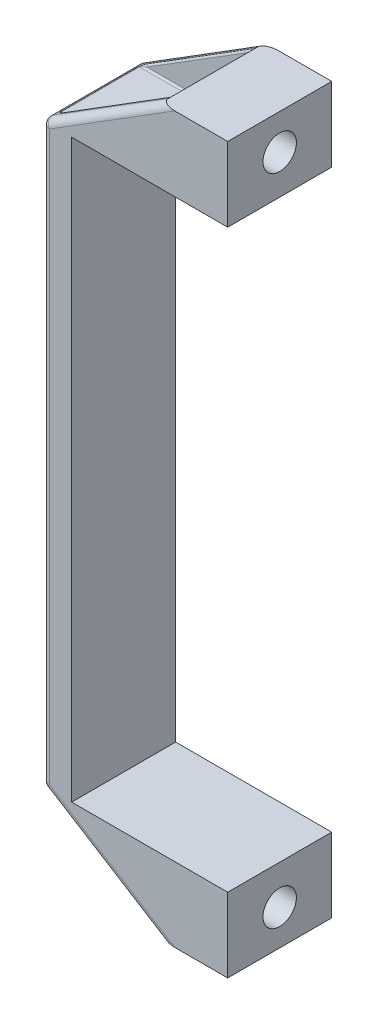
SolidWorks part; units mm, degrees
ref_plane "前视基准面" through (0, 0, 0) normal (0, 0, 1) x (1, 0, 0)
ref_plane "上视基准面" through (0, 0, 0) normal (0, 1, 0) x (1, 0, 0)
ref_plane "右视基准面" through (0, 0, 0) normal (1, 0, 0) x (0, 0, -1)
sketch "草图1" plane through (0, 0, 0) normal (0, 0, 1) x (1, 0, 0)
  line L0 (0, 0) -> (-18, 0)
  line L1 (-18, 0) -> (-50, 20)
  line L2 (-50, 20) -> (-50, 175)
  line L3 (-50, 175) -> (-18, 195)
  line L4 (-18, 195) -> (0, 195)
  line L5 (0, 195) -> (0, 175)
  line L6 (0, 175) -> (-42, 175)
  line L7 (-42, 175) -> (-42, 20)
  line L8 (-42, 20) -> (0, 20)
  line L9 (0, 20) -> (0, 0)
  line L10 (-50, 97.5) -> (24.6077, 97.5) construction
  point P13 (-42, 97.5)
  dimension "D1" = 8
  dimension "D2" = 50
  dimension "D3" = 195
  dimension "D4" = 18
  dimension "D5" = 20
  dimension "D6" = 155
extrude "凸台-拉伸1" add sketch "草图1" along normal mid plane 28
sketch "草图2" plane through (-50, 0, 0) normal (-1, 0, 0) x (0, 0, 1)
  line L1 (-11, 176) -> (11, 176)
  line L2 (-11, 176) -> (-11, 195)
  line L3 (-11, 195) -> (11, 195)
  line L4 (11, 176) -> (11, 195)
  line L7 (14, 195) -> (14, 175) construction
  line L8 (-14, 195) -> (-14, 175) construction
  line L9 (14, 195) -> (-14, 195) construction
  dimension "D1" = 3
  dimension "D2" = 3
  dimension "D3" = 19
extrude "切除-拉伸1" cut sketch "草图2" against normal blind 32
ref_plane "基准面1" through (0, 97.5, 0) normal (0, 1, 0) x (-1, 0, 0)
hole_wizard "打孔尺寸根据内六角花形圆柱头螺钉-4.8级的类型1" positions "草图4" profile "草图3" counterbore size "M8" standard "GB" end condition through all
sketch "草图4" plane through (-18, 0, 0) normal (-1, 0, 0) x (0, 0, 1)
  line L0 (14, 175) -> (14, 20) construction
  point P0 (0, 185.5)
  point P3 (14, 97.5)
  dimension "D1" = 88
sketch "草图3" plane through (-18, 185.5, 0) normal (0, 1, 0) x (0, 0, 1)
  line L0 (0, 0) -> (0, 18)
  line L1 (0, 18) -> (4.5, 18)
  line L3 (4.5, 18) -> (4.5, 6)
  line L4 (4.5, 6) -> (7.5, 6)
  line L5 (7.5, 6) -> (7.5, 0)
  line L7 (7.5, 0) -> (0, 0)
  line L11 (0, -6.35) -> (0, 107.95) construction
  dimension "通孔孔直径" = 9
  dimension "通孔孔深度" = 18
  dimension "柱形沉头孔直径" = 15
  dimension "柱形沉头孔深度" = 6
mirror "镜向1" about plane through (0, 97.5, 0) normal (0, 1, 0) of "打孔尺寸根据内六角花形圆柱头螺钉-4.8级的类型1", "切除-拉伸1"
fillet "圆角1" radius 2 8 edges at (-34, 185, -14) (-34, 185, 14) (-50, 175, 0) (-50, 20, 0) (-34, 10, 14) (-34, 10, -14) (-50, 97.5, -14) (-50, 97.5, 14)
fillet "圆角2" radius 0.5 12 edges at (-33.2, 185.5, 11) (-33.2, 185.5, -11) (-18, 19, 0) (-33.2, 19, -11) (-33.2, 19, 11) (-18, 176, 0) (-33.2, 176, 11) (-33.2, 176, -11) (-33.2, 9.5, 11) (-33.2, 9.5, -11) (-48.4, 176, 0) (-48.4, 19, 0)
